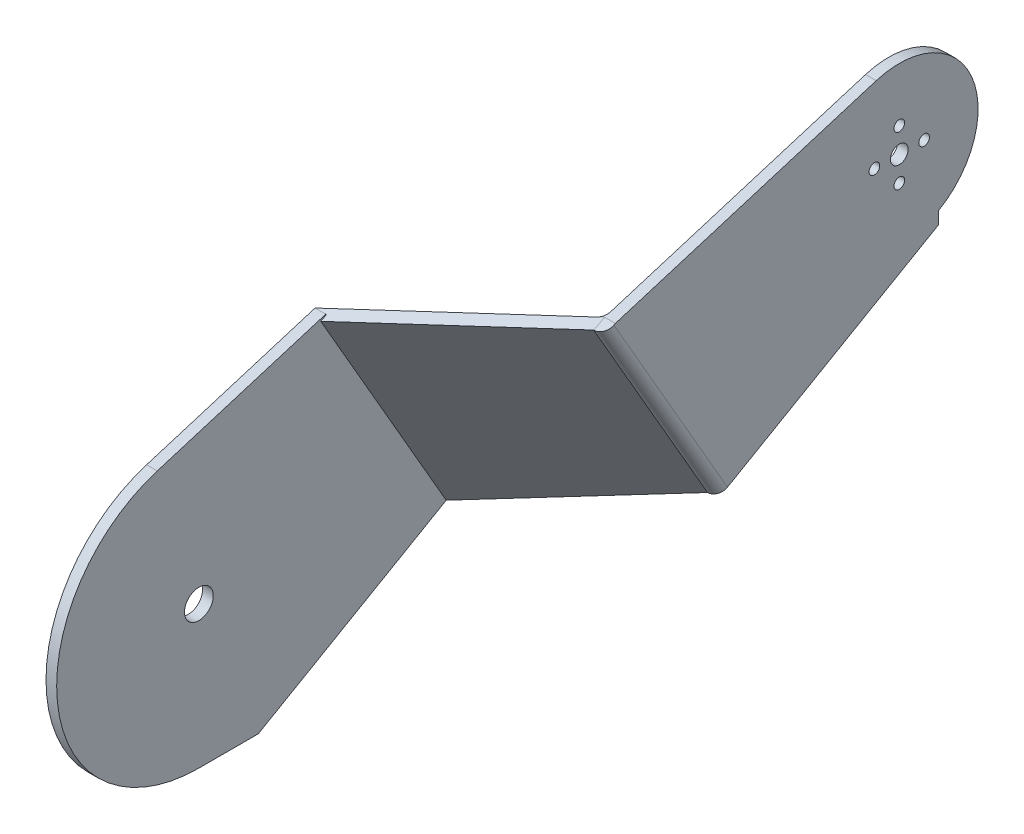
SolidWorks part; units mm, degrees
ref_plane "前视基准面" through (0, 0, 0) normal (0, 0, 1) x (1, 0, 0)
ref_plane "上视基准面" through (0, 0, 0) normal (0, 1, 0) x (1, 0, 0)
ref_plane "右视基准面" through (0, 0, 0) normal (1, 0, 0) x (0, 0, -1)
sketch "草图2" plane through (0, 0, 0) normal (1, 0, 0) x (0, 0, -1)
  line L0 (-11.7006, 38.2504) -> (138.5148, 84.2007)
  line L1 (0, -40) -> (16.7102, -40)
  line L2 (16.7102, -40) -> (120, 19.5373)
  line L3 (156.0716, 43.7921) -> (120, 23)
  line L4 (120, 23) -> (19.9756, -34.6551)
  line L6 (120, 19.5373) -> (156.0716, 40.3294)
  line L7 (156.0716, 43.7921) -> (156.0716, 40.3294)
  circle A0 centre (0, 0) radius 40
  circle A1 centre (145, 63) radius 2.5
  circle A2 centre (145, 63) radius 22.1704
  circle A3 centre (0, 0) radius 3
  circle A4 centre (145, 70) radius 1.5
  circle A5 centre (152, 63) radius 1.5
  circle A6 centre (145, 56) radius 1.5
  circle A7 centre (138, 63) radius 1.5
  point P28 (145, 63)
  dimension "D1" = 80
  dimension "D7" = 5
  dimension "D6" = 44.3408
  dimension "D8" = 6
  dimension "D11" = 3
  dimension "D2" = 120
  dimension "D3" = 23
  dimension "D4" = 25
  dimension "D5" = 40
  dimension "D9" = 3
  dimension "D10" = 16.7102
  dimension "D12" = 7
  dimension "D13" = 4
extrude "凸台-拉伸1" add sketch "草图2" along normal blind 3 contours A0 A3 | A2 A1 | A0 L1 L2 L4 | A2 L0 A0 L4 L3 region at (0, 33.1628, -76.327) region at (0, 31.2466, -23.1176) region at (0, 80.3187, -157.8131) region at (0, 0.2577, -83.4271)
sketch "草图4" plane through (3, 0, 0) normal (1, 0, 0) x (0, 0, -1)
  line L0 (0, -40) -> (16.7102, -40)
  line L1 (16.7102, -40) -> (156.0716, 40.3294)
  line L2 (156.0716, 40.3294) -> (156.0716, 43.7921)
  line L3 (156.0716, 43.7921) -> (19.9756, -34.6551)
  line L4 (156.0716, 43.7921) -> (156.0716, 40.3294) construction
  arc A0 (0, -40) -> (19.9756, -34.6551) centre (0, 0) ccw
extrude "凸台-拉伸2" add sketch "草图4" along normal blind 196
ref_plane "基准面5" through (101, 0, 0) normal (1, 0, 0) x (0, 0, -1)
mirror "镜向2" about plane through (101, 0, 0) normal (1, 0, 0) of "凸台-拉伸1"
sketch "草图5" plane through (202, 0, 0) normal (1, 0, 0) x (0, 0, -1)
  circle A0 centre (0, 0) radius 8
  dimension "D1" = 16
extrude "切除-拉伸1" cut sketch "草图5" against normal blind 10
sketch "草图6" plane through (0, 0, 0) normal (-1, 0, 0) x (0, 0, 1)
  circle A0 centre (0, 0) radius 4.05
  dimension "D1" = 8.1
extrude "切除-拉伸2" cut sketch "草图6" against normal blind 10
ref_plane "基准面3" through (251, 0, 0) normal (1, 0, 0) x (0, 0, -1)
sketch "草图8" plane through (251, 0, 0) normal (1, 0, 0) x (0, 0, -1)
  circle A0 centre (0, 0) radius 40
extrude "凸台-拉伸3" add sketch "草图8" along normal blind 3 separate body
sketch "草图9" plane through (251, 0, 0) normal (1, 0, 0) x (0, 0, -1)
  line L0 (0, -40) -> (16.7102, -40)
  line L1 (0, -40) -> (16.7102, -40) construction
  line L2 (16.7102, -40) -> (53.7479, -18.6511)
  line L3 (16.7102, -40) -> (156.0716, 40.3294) construction
  line L4 (53.7479, -18.6511) -> (52.2498, -16.0519)
  line L5 (156.0716, 43.7921) -> (19.9756, -34.6551) construction
  line L6 (52.2498, -16.0519) -> (19.9756, -34.6551)
  circle A0 centre (0, 0) radius 40 construction
  arc A1 (0, -40) -> (19.9756, -34.6551) centre (0, 0) ccw
extrude "凸台-拉伸4" add sketch "草图9" against normal blind 61 and the other way blind 3
sketch "草图10" plane through (0, -37.2542, -21.4737) normal (0, -0.8664, -0.4994) x (1, 0, 0)
  line L0 (254, -37.2519) -> (254, -57.2519)
  line L2 (254, -57.2519) -> (202, -87.2741)
  line L3 (202, -37.2519) -> (202, -155.3571) construction
  line L4 (202, -87.2741) -> (202, -37.2519)
  line L5 (202, -37.2519) -> (254, -37.2519)
  dimension "D1" = 20
  dimension "D2" = 60
  dimension "D3" = 50.0222
extrude "凸台-拉伸5" add sketch "草图10" against normal blind 3
sketch "草图14" plane through (254, 0, 0) normal (1, 0, 0) x (0, 0, -1)
  line L0 (-11.7006, 38.2504) -> (35.6798, 52.7439)
  line L1 (-11.7006, 38.2504) -> (138.5148, 84.2007) construction
  line L2 (35.6798, 52.7439) -> (69.5773, -6.0641)
  line L3 (69.5773, -6.0641) -> (19.9756, -34.6551)
  line L4 (69.5773, -6.0641) -> (71.0755, -8.6633) construction
  line L5 (16.7102, -40) -> (71.0755, -8.6633) construction
  arc A0 (19.9756, -34.6551) -> (-11.7006, 38.2504) centre (0, 0) ccw
extrude "凸台-拉伸14" add sketch "草图14" against normal blind 3
sketch "草图15" plane through (88.2908, 76.3686, -132.4901) normal (0.5, 0.4325, -0.7503) x (-0.866, 0.2497, -0.4332)
  line L0 (-191.3445, -43) -> (-191.3445, 27.878)
  line L1 (-131.3001, -43) -> (-131.3001, 20.9739)
  line L2 (-170.4548, 38.9825) -> (-93.9096, 3.7768) construction
  line L3 (-131.3001, 20.9739) -> (-191.3445, 27.878)
  line L4 (-191.3445, -43) -> (-131.3001, -43)
extrude "凸台-拉伸15" add sketch "草图15" against normal blind 3
mirror "镜向8" about plane through (101, 0, 0) normal (1, 0, 0) of "凸台-拉伸15"
mirror "镜向10" about plane through (101, 0, 0) normal (1, 0, 0) of "凸台-拉伸5"
mirror "镜向11" about plane through (101, 0, 0) normal (1, 0, 0) of "凸台-拉伸4"
mirror "镜向12" about plane through (101, 0, 0) normal (1, 0, 0) of "凸台-拉伸14"
sketch "草图16" plane through (-52, 0, 0) normal (-1, 0, 0) x (0, 0, 1)
  circle A0 centre (0, 0) radius 40
extrude "凸台-拉伸16" add sketch "草图16" against normal blind 3
sketch "草图17" plane through (202, 0, 0) normal (1, 0, 0) x (0, 0, -1)
  line L0 (-11.1203, 38.4231) -> (61.7391, 60.7153)
  line L1 (62.0375, 60.1977) -> (92.5867, 7.1987)
  line L2 (62.0375, 60.1977) -> (92.5867, 7.1987) construction
  line L3 (92.5867, 7.1987) -> (68.0767, -6.9291) construction
  line L4 (92.5867, 7.1987) -> (19.9756, -34.6551)
  line L5 (65.1382, 61.7551) -> (35.6798, 52.7439) construction
  line L6 (62.0375, 60.1977) -> (65.1382, 61.7551)
  line L7 (65.1382, 61.7551) -> (61.7391, 60.7153)
  arc A0 (-11.1203, 38.4231) -> (19.9756, -34.6551) centre (0, 0) ccw
extrude "切除-拉伸5" cut sketch "草图17" against normal blind 20
sketch "草图18" plane through (0, 38.2504, 11.7006) normal (0, 0.9563, 0.2925) x (1, 0, 0)
  line L0 (199, 76.7989) -> (202, 76.9328)
  line L1 (202, 76.9328) -> (202, 0)
  line L2 (202, 0) -> (199, 0)
  line L3 (199, 0) -> (199, 76.7989)
extrude "切除-拉伸6" cut sketch "草图18" against normal blind 20
sketch "草图21" plane through (3, 0, 0) normal (1, 0, 0) x (0, 0, -1)
  line L0 (92.5867, 7.1987) -> (62.0375, 60.1977)
  line L1 (65.1382, 61.7551) -> (35.6798, 52.7439) construction
  line L2 (61.7391, 60.7153) -> (-11.7006, 38.2504)
  line L3 (92.5867, 7.1987) -> (19.9756, -34.6551)
  line L4 (61.7391, 60.7153) -> (65.1382, 61.7551)
  line L5 (65.1382, 61.7551) -> (138.5148, 84.2007) construction
  line L6 (65.1382, 61.7551) -> (62.0375, 60.1977)
  arc A0 (-11.7006, 38.2504) -> (19.9756, -34.6551) centre (0, 0) ccw
extrude "切除-拉伸7" cut sketch "草图21" along direction (1, 0, 0) on the side against the normal up to next (3 mm away)
fillet "圆角3" radius 3 1 edges at (3, 33.6982, -77.3121) type face fillet first side face at (1.5, 33.6982, -77.3121) second side face at (3, 52.9965, -106.4779)
fillet "圆角4" radius 3 1 edges at (199, 33.6982, -77.3121) type face fillet first side face at (200.5, 33.6982, -77.3121) second side face at (199, 52.9965, -106.4779)
fillet "圆角5" radius 3 1 edges at (202, 34.0423, -81.1121) type face fillet first side face at (202, 63, -147.5) second side face at (228, 28.0413, -67.2449)
fillet "圆角6" radius 3 1 edges at (0, 34.0423, -81.1121) type face fillet first side face at (0, 63, -139.5) second side face at (-26, 28.0413, -67.2449)
sketch "草图22" plane through (254, 0, 0) normal (1, 0, 0) x (0, 0, -1)
  circle A0 centre (0, 0) radius 7.75
  dimension "D1" = 15.5
extrude "切除-拉伸8" cut sketch "草图22" against normal blind 10 contours A0
sketch "草图23" plane through (-52, 0, 0) normal (-1, 0, 0) x (0, 0, 1)
  circle A0 centre (0, 0) radius 4.05
  dimension "D1" = 8.1
extrude "切除-拉伸9" cut sketch "草图23" against normal blind 10
sketch "草图24" plane through (0, -37.2542, -21.4737) normal (0, -0.8664, -0.4994) x (1, 0, 0)
  line L0 (-49, 40) -> (-49, -55.5198)
  line L1 (-49, -55.5198) -> (0, -83.81)
  line L4 (3, -87.2741) -> (3, -179.2567)
  line L5 (3, -179.2567) -> (199, -179.2567)
  line L6 (199, -179.2567) -> (199, -87.2741)
  line L7 (199, -87.2741) -> (199, -86.81)
  line L9 (202, -83.81) -> (251, -55.5198)
  line L10 (251, -42.8868) -> (251, 42.8868) construction
  line L11 (251, 0) -> (251, -55.5198) construction
  line L12 (251, -55.5198) -> (251, 40)
  line L13 (251, 40) -> (-49, 40)
  line L14 (3, -86.81) -> (3, -87.2741)
  arc A0 (3, -86.81) -> (0, -83.81) centre (0, -86.81) ccw
  arc A1 (199, -86.81) -> (202, -83.81) centre (202, -86.81) cw
extrude "切除-拉伸10" cut sketch "草图24" against normal blind 10
sketch "草图25" plane through (254, 0, 0) normal (1, 0, 0) x (0, 0, -1)
  line L1 (-333.6411, 236.6279) -> (181.0618, 236.6279)
  line L2 (-333.6411, 236.6279) -> (-333.6411, -48.9407)
  line L3 (-333.6411, -48.9407) -> (181.0618, -48.9407)
  line L4 (181.0618, 236.6279) -> (181.0618, -48.9407)
  line L5 (-333.6411, 236.6279) -> (181.0618, -48.9407) construction
  line L6 (-333.6411, -48.9407) -> (181.0618, 236.6279) construction
  point P0 (-76.2897, 93.8436)
extrude "切除-拉伸11" cut sketch "草图25" against normal blind 80
